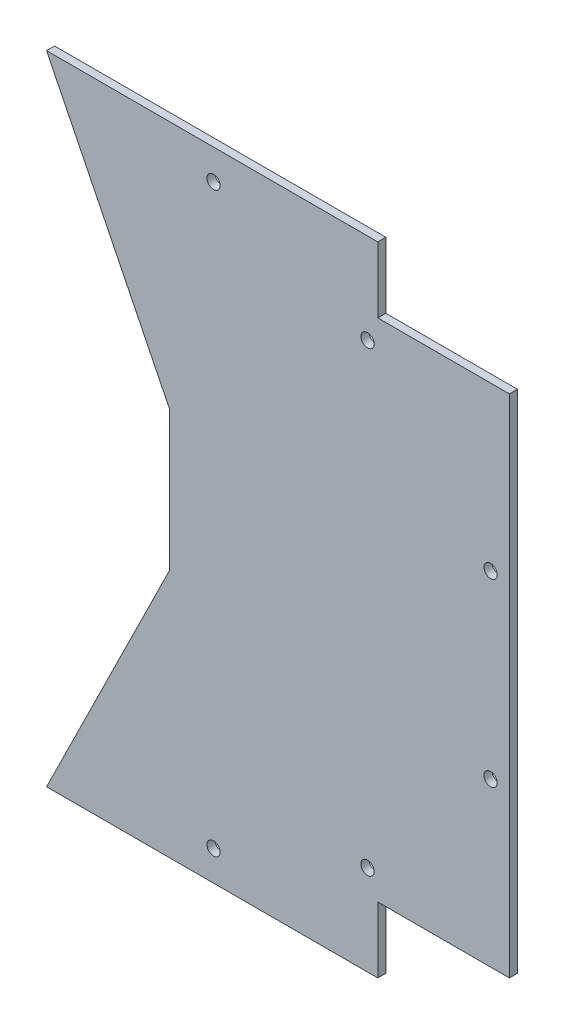
SolidWorks part; units mm, degrees
material "Thornel VCB-20 Carbon Cloth"
ref_plane "Front Plane" through (0, 0, 0) normal (0, 0, 1) x (1, 0, 0)
ref_plane "Top Plane" through (0, 0, 0) normal (0, 1, 0) x (1, 0, 0)
ref_plane "Right Plane" through (0, 0, 0) normal (1, 0, 0) x (0, 0, -1)
sketch "Sketch2" plane through (0, 0, 0) normal (0, 0, 1) x (-1, 0, 0)
  line L11 (-2.9301, 168.7083) -> (38.7094, 168.7083)
  line L12 (-2.9301, 8.6883) -> (38.7094, 8.6883)
  line L13 (38.7094, -12.1397) -> (38.7094, 8.6883)
  line L14 (143.4971, -12.1397) -> (38.7094, -12.1397)
  line L15 (38.7094, 189.5363) -> (38.7094, 168.7083)
  line L16 (143.4971, 189.5363) -> (38.7094, 189.5363)
  line L17 (104.6174, 110.8598) -> (143.4971, 189.5363)
  line L18 (104.6174, 66.5368) -> (143.4971, -12.1397)
  line L19 (104.6174, 66.5368) -> (72.8674, 66.5368)
  line L20 (72.8674, 66.5368) -> (72.8674, 110.8598)
  line L21 (104.6174, 110.8598) -> (72.8674, 110.8598)
  line L22 (-2.9301, 168.7083) -> (-2.9301, 8.6883)
  line L23 (41.9566, 19.6103) -> (41.9566, 13.2603) construction
  circle A0 centre (41.9566, 160.9613) radius 2.0955
  circle A1 centre (90.6739, 180.0113) radius 2.0955
  circle A2 centre (90.6739, -2.6147) radius 2.0955
  circle A3 centre (3.0351, 117.2098) radius 2.0955
  circle A4 centre (3.0351, 60.1868) radius 2.0955
  circle A5 centre (41.9566, 16.4353) radius 2.0955
  point P22 (0, 0)
  point P36 (41.9566, 16.4353)
  dimension "D1" = 4.191
  dimension "D2" = 4.191
  dimension "D3" = 4.191
  dimension "D4" = 4.191
  dimension "D5" = 4.191
  dimension "D6" = 4.191
  dimension "D7" = 31.75
  dimension "D8" = 41.6395
  dimension "D9" = 20.828
  dimension "D10" = 160.02
  dimension "D11" = 20.828
  dimension "D12" = 41.6395
  dimension "D13" = 104.7876
  dimension "D14" = 116.297
  dimension "D15" = 116.297
  dimension "D16" = 44.323
  dimension "D17" = 26.297
  dimension "D18" = 9.525
  dimension "D19" = 28.575
  dimension "D20" = 7.747
  dimension "D21" = 51.9645
  dimension "D22" = 51.4985
  dimension "D23" = 5.9651
  dimension "D24" = 51.4985
  dimension "D25" = 5.9651
  dimension "D26" = 7.747
  dimension "D27" = 3.2471
  dimension "D28" = 9.525
  dimension "D29" = 51.9645
extrude "Boss-Extrude1" add sketch "Sketch2" along normal blind 2.54
sketch "Sketch3" plane through (0, 0, 2.54) normal (0, 0, 1) x (1, 0, 0)
  line L1 (-104.6174, -66.5368) -> (-72.8674, -66.5368)
  line L2 (-104.6174, -66.5368) -> (-104.6174, -110.8598)
  line L3 (-104.6174, -110.8598) -> (-72.8674, -110.8598)
  line L4 (-72.8674, -66.5368) -> (-72.8674, -110.8598)
extrude "Boss-Extrude2" add sketch "Sketch3" against normal up to surface (2.54 mm away) up to face at (-65.9118, -88.6983, 0)
